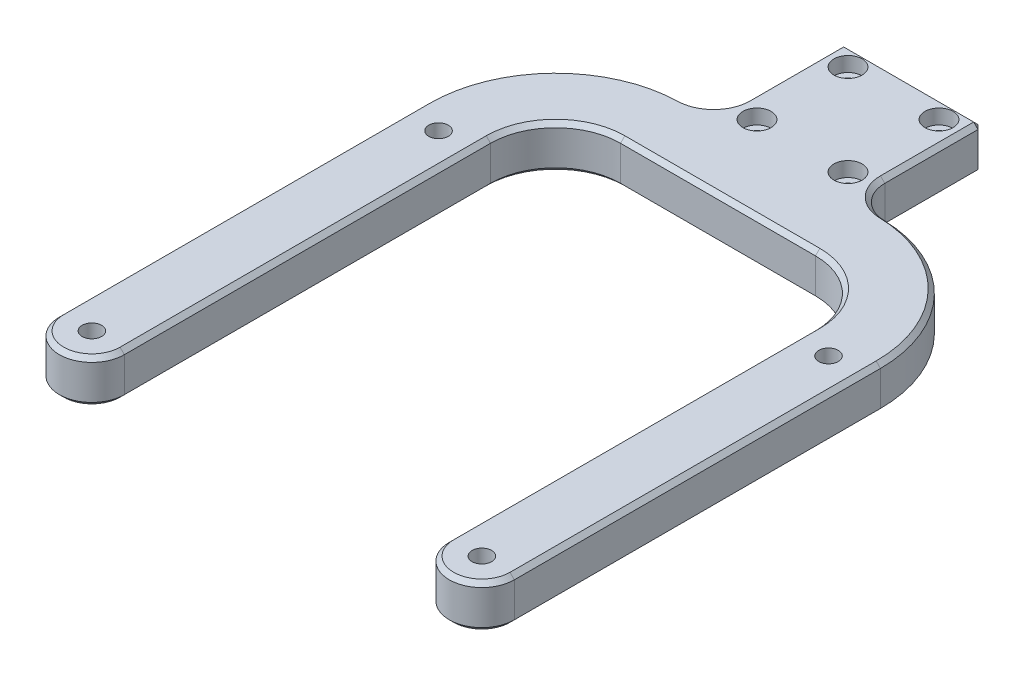
SolidWorks part; units mm, degrees
material "ABS PC"
ref_plane "Front Plane" through (0, 0, 0) normal (0, 0, 1) x (1, 0, 0)
ref_plane "Top Plane" through (0, 0, 0) normal (0, 1, 0) x (1, 0, 0)
ref_plane "Right Plane" through (0, 0, 0) normal (1, 0, 0) x (0, 0, -1)
sketch "Sketch1" plane through (0, 0, 0) normal (0, 1, 0) x (1, 0, 0)
  line L0 (22.5, 57.25) -> (0, 57.25)
  line L1 (0, 57.25) -> (0, 102.25)
  line L2 (37.5, 42.25) -> (37.5, -42.25)
  line L7 (16, 102.25) -> (0, 102.25)
  line L8 (0, 0) -> (0, 57.25) construction
  line L9 (16, 102.25) -> (16, 72.25)
  line L13 (16, 72.25) -> (22.5, 72.25)
  line L14 (52.5, 42.25) -> (52.5, -42.25)
  arc A4 (22.5, 57.25) -> (37.5, 42.25) centre (22.5, 42.25) cw
  arc A6 (22.5, 72.25) -> (52.5, 42.25) centre (22.5, 42.25) cw
  arc A9 (37.5, -42.25) -> (52.5, -42.25) centre (45, -42.25) ccw
  circle A10 centre (45, 37.75) radius 2.25
  circle A11 centre (45, -42.25) radius 2.25
  point P10 (37.5, 0)
  dimension "D7" = 80
  dimension "D8" = 30
  dimension "D9" = 15
  dimension "D6" = 107
  dimension "D14" = 4.5
  dimension "D1" = 15
  dimension "D2" = 15
  dimension "D3" = 30
  dimension "D4" = 32
  dimension "D5" = 75
extrude "Boss-Extrude1" add sketch "Sketch1" along normal blind 10
fillet "Fillet1" radius 7.5 1 edges at (16, 5, -72.25)
chamfer "Chamfer1" distance 1 angle 45 19 edges at (11.25, 0, -57.25) (33.1066, 0, -52.8566) (37.5, 0, 0) (52.5, 0, 0) (43.9942, 0, -63.1784) (16, 0, -90.9933) (8, 0, -102.25) (11.25, 10, -57.25) (33.1066, 10, -52.8566) (37.5, 10, 0) (52.5, 10, 0) (43.9942, 10, -63.1784) (16, 10, -90.9933) (8, 10, -102.25) (18.1265, 0, -74.5046) (18.1265, 10, -74.5046) (16, 5, -102.25) (45, 0, 49.75) (45, 10, 49.75)
sketch "Sketch5" plane through (0, 0, 0) normal (0, -1, 0) x (1, 0, 0)
  circle A0 centre (45, -37.75) radius 2.25 construction
  circle A1 centre (45, 42.25) radius 2.25 construction
  circle A2 centre (45, -37.75) radius 2.25
  circle A3 centre (45, 42.25) radius 2.25
extrude "Boss-Extrude2" add sketch "Sketch5" against normal offset from surface (4 mm away) 6 up to face at (26.3251, 10, -47.0845)
mirror "Mirror1" about plane through (0, 10, -57.25) normal (1, 0, 0) of bodies 104 101
sketch "Sketch6" plane through (0, 10, 0) normal (0, 1, 0) x (1, 0, 0)
  line L0 (-15, 102.25) -> (15, 102.25) construction
  line L1 (-16, 102.25) -> (16, 102.25) construction
  line L2 (-16, 102.25) -> (-16, 72.25) construction
  line L3 (-16, 72.25) -> (16, 72.25) construction
  line L4 (16, 102.25) -> (16, 72.25) construction
  line L5 (16, 101.25) -> (16, 79.7367) construction
  line L7 (-10.5, 97.75) -> (10.5, 97.75) construction
  line L8 (-10.5, 97.75) -> (-10.5, 76.75) construction
  line L9 (-10.5, 76.75) -> (10.5, 76.75) construction
  line L10 (10.5, 97.75) -> (10.5, 76.75) construction
  circle A0 centre (10.5, 97.75) radius 1.5 construction
  circle A1 centre (10.5, 76.75) radius 1.5 construction
  circle A2 centre (-10.5, 97.75) radius 1.5 construction
  circle A3 centre (-10.5, 76.75) radius 1.5 construction
  point P14 (10.5, 76.75)
  point P16 (10.5, 76.75)
  point P18 (10.5, 76.75)
  dimension "D3" = 3
  dimension "D4" = 18
  dimension "D5" = 3
  dimension "D6" = 4
  dimension "D7" = 18
  dimension "D1" = 32
  dimension "D2" = 30
hole_wizard "CBORE for M3 Hex Socket Head Cap Screw1" positions "Sketch7" profile "Sketch8" counterbore size "M3" standard "ISO" end condition through all
sketch "Sketch7" plane through (0, 10, 0) normal (0, 1, 0) x (1, 0, 0)
  point P0 (10.5, 97.75)
  point P3 (-10.5, 97.75)
  point P6 (-10.5, 76.75)
  point P9 (10.5, 76.75)
  point P12 (0, 0)
sketch "Sketch8" plane through (10.5, 10, -97.75) normal (1, 0, 0) x (0, 0, 1)
  line L0 (0, 0) -> (0, 10)
  line L1 (0, 10) -> (1.7, 10)
  line L3 (1.7, 10) -> (1.7, 3.4)
  line L4 (1.7, 3.4) -> (3.25, 3.4)
  line L5 (3.25, 3.4) -> (3.25, 0)
  line L7 (3.25, 0) -> (0, 0)
  line L11 (0, -6.35) -> (0, 107.95) construction
  dimension "Thru Hole Dia." = 3.4
  dimension "Thru Hole Depth" = 10
  dimension "C'Bore Dia." = 6.5
  dimension "C'Bore Depth" = 3.4
